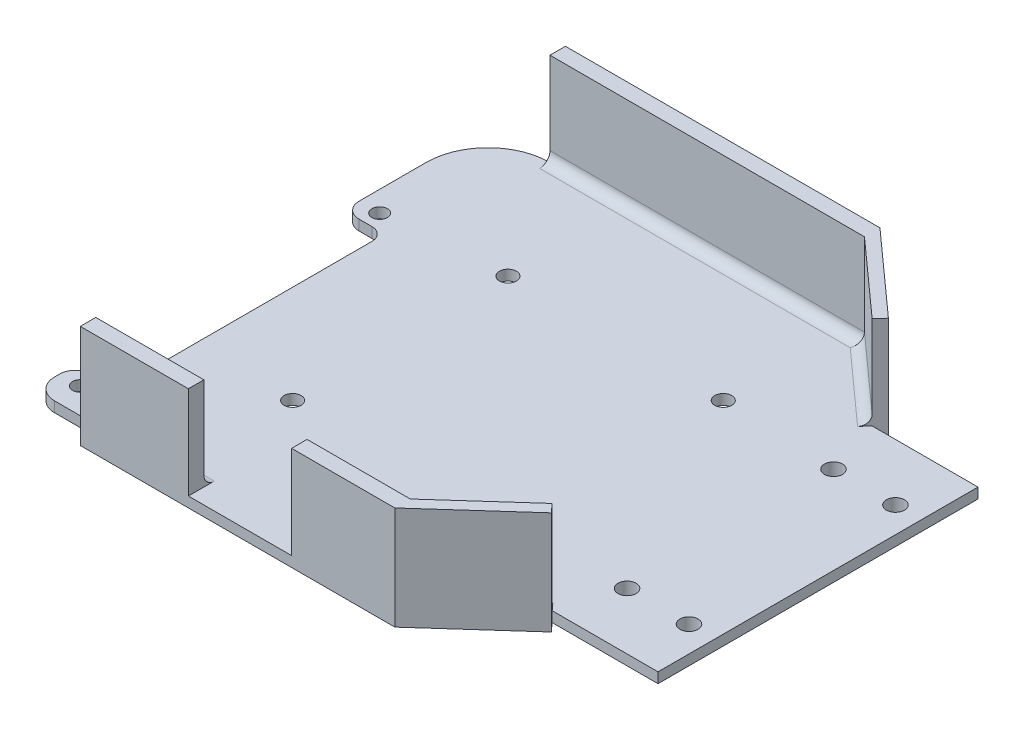
SolidWorks part; units mm, degrees
ref_plane "Front Plane" through (0, 0, 0) normal (0, 0, 1) x (1, 0, 0)
ref_plane "Top Plane" through (0, 0, 0) normal (0, 1, 0) x (1, 0, 0)
ref_plane "Right Plane" through (0, 0, 0) normal (1, 0, 0) x (0, 0, -1)
sketch "Croquis1" plane through (0, 0, 0) normal (0, 1, 0) x (1, 0, 0)
  line L0 (18.97, 54) -> (33.46, 41)
  line L1 (-41.97, 54) -> (41.97, 54)
  line L2 (-53.97, 42) -> (-53.97, -34)
  line L3 (-53.97, -34) -> (41.97, -34)
  line L4 (53.97, 42) -> (53.97, -22)
  line L5 (33.46, 41) -> (53.97, 41)
  line L6 (18.97, -34) -> (33.46, -21)
  line L8 (53.97, 7.5931) -> (53.97, 12.4069)
  line L9 (33.46, -21) -> (53.97, -21)
  circle A0 centre (-49.97, 29) radius 1.5
  circle A1 centre (-49.97, -29) radius 1.5
  circle A4 centre (-26.97, 30.86) radius 1.65
  circle A5 centre (14.75, 30.86) radius 1.65
  circle A6 centre (14.75, -10.86) radius 1.65
  circle A7 centre (-26.97, -10.86) radius 1.65
  arc A12 (41.97, -34) -> (53.97, -22) centre (41.97, -22) ccw
  arc A13 (41.97, 54) -> (53.97, 42) centre (41.97, 42) cw
  arc A14 (-41.97, 54) -> (-53.97, 42) centre (-41.97, 42) ccw
  point P0 (0, 0)
  point P14 (53.97, 10)
  point P38 (0, 54)
  point P41 (53.97, 10)
  point P51 (53.97, -34)
  dimension "D18" = 3.3
  dimension "D25" = 12
  dimension "D6" = 3
  dimension "D2" = 107.94
  dimension "D4" = 58
  dimension "D5" = 29
  dimension "D9" = 4
  dimension "D13" = 34
  dimension "D15" = 41.72
  dimension "D16" = 41.72
  dimension "D14" = 88
  dimension "D19" = 27
  dimension "D3" = 62
  dimension "D7" = 13
  dimension "D8" = 35
  dimension "D10" = 20.51
  dimension "D11" = 23.14
extrude "Saliente-Extruir1" add sketch "Croquis1" along normal blind 2 contours L4 | L1 A14 L2 L3 A12 L4 A13 A0 A1 A4 A5 A6 A7 region at (-3.0127, 0, -9.8694)
fillet "Redondeo1" radius 4 1 edges at (-53.97, 1, 34)
sketch "Croquis4" plane through (0, 2, 0) normal (0, 1, 0) x (1, 0, 0)
  line L0 (-53.97, 26) -> (-53.97, -26)
  line L1 (-53.97, 42) -> (-53.97, -30) construction
  line L2 (-53.97, -26) -> (-48.47, -26)
  line L3 (-45.97, -23.5) -> (-45.97, 23.5)
  line L4 (-48.47, 26) -> (-53.97, 26)
  arc A0 (-48.47, -26) -> (-45.97, -23.5) centre (-48.47, -23.5) ccw
  arc A1 (-45.97, 23.5) -> (-48.47, 26) centre (-48.47, 23.5) ccw
  circle A2 centre (-49.97, -29) radius 1.5 construction
  circle A4 centre (-49.97, 29) radius 1.5 construction
  dimension "D1" = 3
  dimension "D2" = 2.5
  dimension "D4" = 2.5
  dimension "D3" = 8
  dimension "D5" = 3
extrude "Cortar-Extruir1" cut sketch "Croquis4" against normal through all
fillet "Redondeo2" radius 3 2 edges at (-53.97, 1, 26) (-53.97, 1, -26)
sketch "Croquis5" plane through (0, 2, 0) normal (0, 1, 0) x (1, 0, 0)
  line L0 (53.97, 41) -> (53.97, -21) construction
  circle A0 centre (36.97, 30) radius 1.75
  circle A1 centre (36.97, -10) radius 1.75
  circle A2 centre (48.97, 30) radius 1.75
  circle A3 centre (48.97, -10) radius 1.75
  point P15 (53.97, 10)
  dimension "D3" = 12
  dimension "D4" = 3.5
  dimension "D5" = 20
  dimension "D1" = 40
  dimension "D2" = 5
extrude "Cortar-Extruir2" cut sketch "Croquis5" against normal through all
sketch "Croquis6" plane through (0, 0, 0) normal (0, -1, 0) x (1, 0, 0)
  circle A0 centre (36.97, 10) radius 2.75
  circle A1 centre (36.97, -30) radius 2.75
  circle A2 centre (48.97, -30) radius 2.75
  circle A3 centre (48.97, 10) radius 2.75
  circle A4 centre (36.97, -30) radius 1.75 construction
  circle A5 centre (48.97, -30) radius 1.75 construction
  circle A6 centre (48.97, 10) radius 1.75 construction
  circle A7 centre (36.97, 10) radius 1.75 construction
  circle A8 centre (48.97, -30) radius 1.75
  circle A9 centre (36.97, -30) radius 1.75
  circle A10 centre (48.97, 10) radius 1.75
  circle A11 centre (36.97, 10) radius 1.75
  dimension "D1" = 1
extrude "Saliente-Extruir6" add sketch "Croquis6" along normal blind 2
sketch "Croquis7" plane through (0, 0, 0) normal (0, 1, 0) x (1, 0, 0)
  line L0 (-49.97, -34) -> (18.97, -34) construction
  line L1 (-41.97, -34) -> (18.97, -34)
  line L2 (-41.97, -34) -> (-41.97, -37)
  line L3 (-41.97, -37) -> (18.97, -37)
  line L5 (18.97, -34) -> (33.46, -21)
  line L6 (33.46, -21) -> (34.9512, -22.6621)
  line L7 (34.9512, -22.6621) -> (18.97, -37)
  line L8 (18.97, -34) -> (33.46, -21) construction
  line L10 (-41.97, 54) -> (18.97, 54) construction
  line L11 (-41.97, 54) -> (18.97, 54)
  line L12 (-41.97, 54) -> (-41.97, 57)
  line L13 (-41.97, 57) -> (18.97, 57)
  line L15 (18.97, 54) -> (33.46, 41)
  line L16 (33.46, 41) -> (34.9512, 42.6621)
  line L17 (34.9512, 42.6621) -> (18.97, 57)
  line L18 (18.97, 54) -> (33.46, 41) construction
  point P7 (0, 0)
  point P15 (0, 0)
  point P16 (34.9512, 42.4234)
  dimension "D1" = 3
  dimension "D3" = 3
extrude "Saliente-Extruir7" add sketch "Croquis7" along normal blind 20
sketch "Croquis8" plane through (0, 0, 37) normal (0, 0, 1) x (1, 0, 0)
  line L0 (-41.97, 20) -> (18.97, 20) construction
  line L1 (-21.03, 20) -> (-1.03, 20)
  line L2 (-21.03, 20) -> (-21.03, 2)
  line L3 (-21.03, 2) -> (-1.03, 2)
  line L4 (-1.03, 20) -> (-1.03, 2)
  line L5 (-49.97, 2) -> (-41.97, 2) construction
  line L6 (18.97, 20) -> (18.97, 0) construction
  dimension "D1" = 20
  dimension "D2" = 20
extrude "Cortar-Extruir3" cut sketch "Croquis8" against normal up to next
fillet "Redondeo3" radius 2 5 edges at (26.215, 2, 27.5) (8.97, 2, 34) (-31.5, 2, 34) (26.215, 2, -47.5) (-11.5, 2, -54)
equation "\"D5@Croquis1\"=\"D4@Croquis1\"/2"
equation "\"D14@Croquis1\"=101.54-(6.77*2)"
equation "\"D7@Croquis1\"=\"D14@Croquis1\"/2-31"
equation "\"D11@Croquis1\"=\"D14@Croquis1\"/2-\"D15@Croquis1\"/2"
